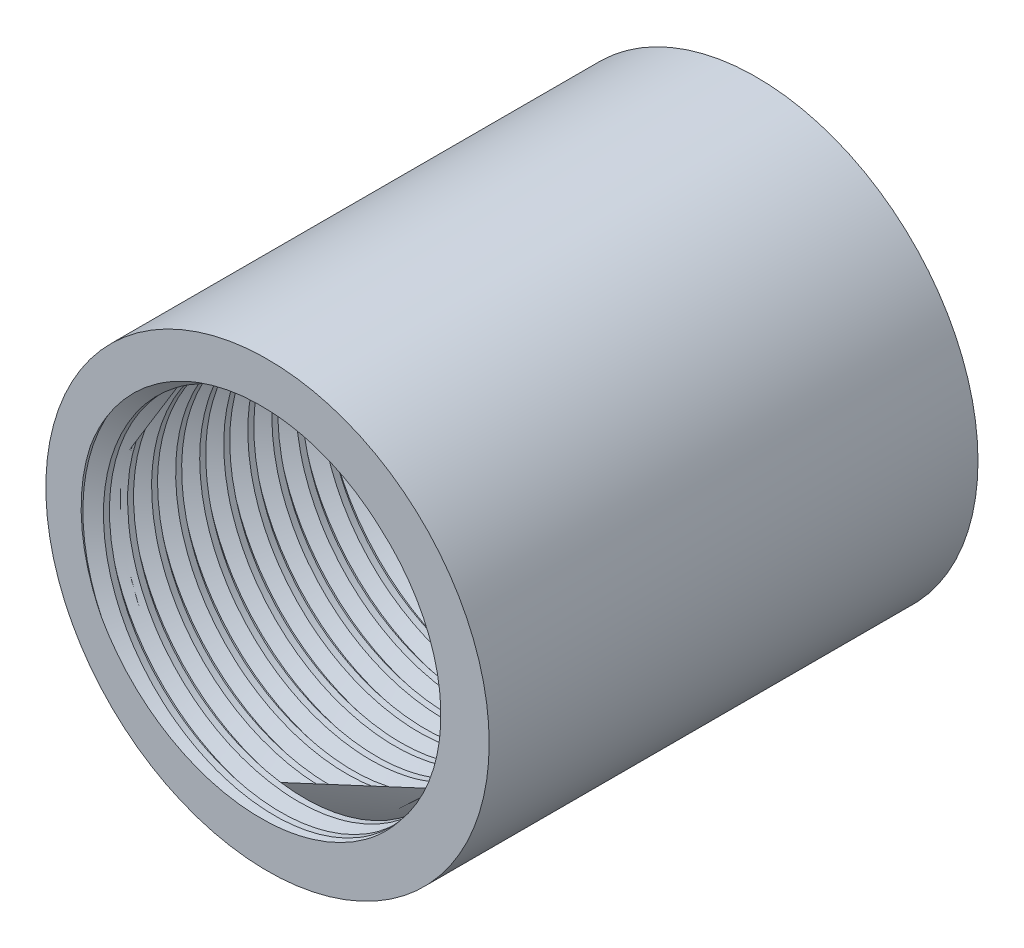
SolidWorks part; units mm, degrees
ref_plane "Płaszczyzna przednia" through (0, 0, 0) normal (0, 0, 1) x (1, 0, 0)
ref_plane "Płaszczyzna górna" through (0, 0, 0) normal (0, 1, 0) x (1, 0, 0)
ref_plane "Płaszczyzna prawa" through (0, 0, 0) normal (1, 0, 0) x (0, 0, -1)
sketch "Szkic1" plane through (0, 0, 0) normal (0, 0, 1) x (1, 0, 0)
  circle A0 centre (0, 0) radius 19.5
  circle A1 centre (0, 0) radius 15.25
  point P5 (0, 0)
  dimension "D1" = 39
  dimension "D2" = 30.5
extrude "Dodanie-wyciągnięcie1" add sketch "Szkic1" along normal blind 43
thread "Gwint1" pitch 2.1167 method cut trim with start face yes trim with end face yes profile "Profil gwintu1" start angle 0, offset 5, length 0, pitch 2.1167, diameter 30.5
ref_plane "Płaszczyzna1" through (-15.25, 0, 48) normal (0, -1, 0) x (-1, 0, 0)
sketch "Profil gwintu1" plane through (-15.25, 0, 48) normal (0, -1, 0) x (-1, 0, 0)
  line L0 (0, 0) -> (0, 2.1167) construction
  line L1 (0, 0) -> (1.1457, 0.6615)
  line L2 (1.1457, 0.6615) -> (1.1457, 0.926)
  line L3 (1.1457, 0.926) -> (0, 1.5875)
  line L4 (1.1457, 0.7937) -> (0, 0.7937) construction
  line L11 (0, 0) -> (0, 1.5875)
  point P2 (0, 0)
  dimension "Pitch" = 2.1167
  dimension "Profile_Angle" = 60
  dimension "Profile_Land" = 0.2646
  dimension "Profile_Height" = 1.1457
